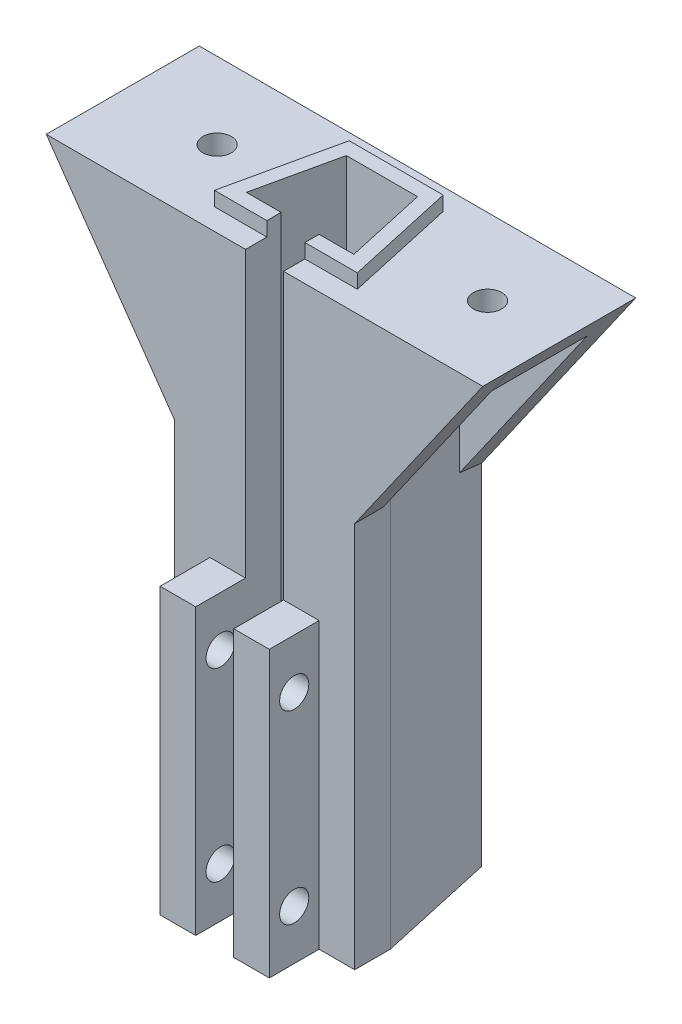
SolidWorks part; units mm, degrees
ref_plane "Front Plane" through (0, 0, 0) normal (0, 0, 1) x (1, 0, 0)
ref_plane "Top Plane" through (0, 0, 0) normal (0, 1, 0) x (1, 0, 0)
ref_plane "Right Plane" through (0, 0, 0) normal (1, 0, 0) x (0, 0, -1)
sketch "Sketch2" plane through (0, 0, 0) normal (0, 1, 0) x (1, 0, 0)
  line L0 (-10.5836, 6.3436) -> (7.4423, 6.3436)
  line L1 (-10.5836, 6.3436) -> (-10.5836, 1.3436)
  line L2 (7.4423, 6.3436) -> (7.4423, 1.3436)
  line L3 (-10.5836, 1.3436) -> (7.4423, 1.3436)
  line L4 (7.4423, 6.3436) -> (11.1002, -10.1564)
  line L5 (7.4423, 6.3436) -> (2.5608, 5.2614)
  line L6 (11.1002, -10.1564) -> (6.2187, -11.2386)
  line L7 (2.5608, 5.2614) -> (6.2187, -11.2386)
  line L8 (-10.5836, 6.3436) -> (-14.2416, -10.1564)
  line L9 (-10.5836, 6.3436) -> (-5.7021, 5.2614)
  line L10 (-14.2416, -10.1564) -> (-9.3601, -11.2386)
  line L11 (-5.7021, 5.2614) -> (-9.3601, -11.2386)
  line L12 (-14.2416, -10.1564) -> (-4.2416, -10.1564)
  line L13 (-14.2416, -10.1564) -> (-14.2416, -15.1564)
  line L14 (-4.2416, -10.1564) -> (-4.2416, -15.1564)
  line L15 (-14.2416, -15.1564) -> (-4.2416, -15.1564)
  line L16 (11.1002, -10.1564) -> (1.1002, -10.1564)
  line L17 (11.1002, -10.1564) -> (11.1002, -15.1564)
  line L18 (1.1002, -10.1564) -> (1.1002, -15.1564)
  line L19 (11.1002, -15.1564) -> (1.1002, -15.1564)
  line L20 (-4.2416, -15.1564) -> (-9.2416, -15.1564)
  line L21 (-4.2416, -15.1564) -> (-4.2416, -22.1564)
  line L22 (-9.2416, -15.1564) -> (-9.2416, -22.1564)
  line L23 (-4.2416, -22.1564) -> (-9.2416, -22.1564)
  line L24 (1.1002, -15.1564) -> (6.1002, -15.1564)
  line L25 (1.1002, -15.1564) -> (1.1002, -22.1564)
  line L26 (6.1002, -15.1564) -> (6.1002, -22.1564)
  line L27 (1.1002, -22.1564) -> (6.1002, -22.1564)
  point P0 (-6.5707, 1.3436)
  point P21 (3.4293, 1.3436)
  point P24 (5.9788, -10.1564)
  point P25 (-9.1202, -10.1564)
  dimension "D1" = 0
  dimension "D2" = 5
  dimension "D3" = 5
  dimension "D4" = 5
  dimension "D5" = 10
  dimension "D6" = 360
  dimension "D7" = 11.5
  dimension "D8" = 5
  dimension "D9" = 5
  dimension "D10" = 11.5
  dimension "D11" = 5
  dimension "D12" = 5
  dimension "D13" = 102.5
  dimension "D14" = 10
  dimension "D15" = 10
  dimension "D16" = 102.5
  dimension "D17" = 15.099
  dimension "D18" = 5.3418
  dimension "D19" = 7
  dimension "D20" = 7
extrude "Boss-Extrude1" add sketch "Sketch2" along normal blind 40 contours L16 L4 L2 L3 L7 | L9 L11 L3 L7 L5 L0 | L8 L12 L11 L3 L1 | L5 L7 L3 L2 | L11 L9 L1 L3 | L13 L15 L14 L12 L11 L10 | L12 L10 L11 | L6 L16 L7 | L19 L17 L6 L7 L16 L18 | L25 L27 L26 L19 | L23 L21 L15 L22 region at (-8.4324, 0, -3.6632) region at (-10.4307, 0, 4.0731) region at (-1.5707, 0, -3.9883) region at (7.2894, 0, 4.0731) region at (5.291, 0, -3.6632) region at (-10.9073, 0, 10.5172) region at (-9.1438, 0, 12.7819) region at (6.0025, 0, 12.7819) region at (7.7659, 0, 10.5172) region at (-6.7416, 0, 18.6564) region at (3.6002, 0, 18.6564)
sketch "Sketch3" plane through (-9.2416, 0, 0) normal (-1, 0, 0) x (0, 0, 1)
  line L0 (22.1564, 40) -> (22.1564, 0) construction
  line L1 (15.1564, 40) -> (15.1564, 0) construction
  line L2 (15.1564, 40) -> (22.1564, 40) construction
  line L3 (15.1564, 0) -> (22.1564, 0) construction
  circle A0 centre (18.6564, 33) radius 2.05
  circle A1 centre (18.6564, 7) radius 2.05
  dimension "D5" = 4.1
  dimension "D6" = 4.1
  dimension "D1" = 3.5
  dimension "D2" = 3.5
  dimension "D3" = 3.5
  dimension "D4" = 3.5
  dimension "D7" = 7
  dimension "D8" = 7
extrude "Cut-Extrude2" cut sketch "Sketch3" against normal blind 40
sketch "Sketch4" plane through (0, 40, 0) normal (0, 1, 0) x (1, 0, 0)
  line L0 (-9.1202, -10.1564) -> (-6.5707, 1.3436)
  line L1 (-6.5707, 1.3436) -> (3.4293, 1.3436)
  line L2 (3.4293, 1.3436) -> (5.9788, -10.1564)
  line L3 (5.9788, -10.1564) -> (1.1002, -10.1564)
  line L4 (1.1002, -10.1564) -> (1.1002, -15.1564)
  line L5 (1.1002, -10.1564) -> (1.1002, -22.1564) construction
  line L6 (1.1002, -15.1564) -> (11.1002, -15.1564)
  line L7 (11.1002, -15.1564) -> (11.1002, -10.1564)
  line L8 (11.1002, -10.1564) -> (7.4423, 6.3436)
  line L9 (7.4423, 6.3436) -> (-10.5836, 6.3436)
  line L10 (-10.5836, 6.3436) -> (-14.2416, -10.1564)
  line L11 (-14.2416, -10.1564) -> (-14.2416, -15.1564)
  line L12 (-14.2416, -15.1564) -> (-4.2416, -15.1564)
  line L13 (-4.2416, -10.1564) -> (-4.2416, -22.1564) construction
  line L14 (-4.2416, -15.1564) -> (-4.2416, -10.1564)
  line L33 (-6.5707, 1.3436) -> (3.4293, 1.3436)
  line L34 (3.4293, 1.3436) -> (5.9788, -10.1564)
  line L35 (5.9788, -10.1564) -> (1.1002, -10.1564)
  line L36 (1.1002, -10.1564) -> (1.1002, -22.1564)
  line L37 (1.1002, -22.1564) -> (6.1002, -22.1564)
  line L38 (6.1002, -22.1564) -> (6.1002, -15.1564)
  line L39 (6.1002, -15.1564) -> (11.1002, -15.1564)
  line L40 (11.1002, -15.1564) -> (11.1002, -10.1564)
  line L41 (11.1002, -10.1564) -> (7.4423, 6.3436)
  line L42 (7.4423, 6.3436) -> (-10.5836, 6.3436)
  line L43 (-10.5836, 6.3436) -> (-14.2416, -10.1564)
  line L44 (-14.2416, -10.1564) -> (-14.2416, -15.1564)
  line L45 (-14.2416, -15.1564) -> (-9.2416, -15.1564)
  line L46 (-9.2416, -15.1564) -> (-9.2416, -22.1564)
  line L47 (-9.2416, -22.1564) -> (-4.2416, -22.1564)
  line L48 (-4.2416, -22.1564) -> (-4.2416, -10.1564)
  line L49 (-4.2416, -10.1564) -> (-9.1202, -10.1564)
  line L50 (-9.1202, -10.1564) -> (-6.5707, 1.3436)
  line L51 (-6.5707, 1.3436) -> (3.4293, 1.3436)
  line L52 (3.4293, 1.3436) -> (5.9788, -10.1564)
  line L53 (5.9788, -10.1564) -> (1.1002, -10.1564)
  line L54 (1.1002, -10.1564) -> (1.1002, -22.1564)
  line L55 (1.1002, -22.1564) -> (6.1002, -22.1564)
  line L56 (6.1002, -22.1564) -> (6.1002, -15.1564)
  line L57 (6.1002, -15.1564) -> (11.1002, -15.1564)
  line L58 (11.1002, -15.1564) -> (11.1002, -10.1564)
  line L59 (11.1002, -10.1564) -> (7.4423, 6.3436)
  line L60 (7.4423, 6.3436) -> (-10.5836, 6.3436)
  line L61 (-10.5836, 6.3436) -> (-14.2416, -10.1564)
  line L62 (-14.2416, -10.1564) -> (-14.2416, -15.1564)
  line L63 (-14.2416, -15.1564) -> (-9.2416, -15.1564)
  line L64 (-9.2416, -15.1564) -> (-9.2416, -22.1564)
  line L65 (-9.2416, -22.1564) -> (-4.2416, -22.1564)
  line L66 (-4.2416, -22.1564) -> (-4.2416, -10.1564)
  line L68 (-9.1202, -10.1564) -> (-6.5707, 1.3436)
  line M19 (-6.5707, 1.3436) -> (3.4293, 1.3436)
  line M20 (3.4293, 1.3436) -> (5.9788, -10.1564)
  line M21 (5.9788, -10.1564) -> (1.1002, -10.1564)
  line M22 (1.1002, -10.1564) -> (1.1002, -22.1564)
  line M25 (6.1002, -15.1564) -> (11.1002, -15.1564)
  line M26 (11.1002, -15.1564) -> (11.1002, -10.1564)
  line M27 (11.1002, -10.1564) -> (7.4423, 6.3436)
  line M28 (7.4423, 6.3436) -> (-10.5836, 6.3436)
  line M29 (-10.5836, 6.3436) -> (-14.2416, -10.1564)
  line M30 (-14.2416, -10.1564) -> (-14.2416, -15.1564)
  line M31 (-14.2416, -15.1564) -> (-9.2416, -15.1564)
  line M34 (-4.2416, -22.1564) -> (-4.2416, -10.1564)
  line M35 (-4.2416, -10.1564) -> (-9.1202, -10.1564)
  line M36 (-9.1202, -10.1564) -> (-6.5707, 1.3436)
  dimension "D1" = 0
extrude "Boss-Extrude2" add sketch "Sketch4" along normal blind 40 contours L12 L6 M31 M34 M35 M36 M19 M20 M21 M22 M25 M26 M27 M28 M29 M30 region at (-6.6809, 40, 10.4888)
sketch "Sketch7" plane through (0, 0, -6.3436) normal (0, 0, -1) x (-1, 0, 0)
  line L0 (-7.4423, 82) -> (-7.4423, 0) construction
  line L1 (3.3202, 3.2) -> (-0.1798, 3.2)
  line L2 (3.3202, 3.2) -> (3.3202, 4.4)
  line L3 (3.3202, 4.4) -> (-0.1798, 4.4)
  line L4 (-0.1798, 3.2) -> (-0.1798, 4.4)
  line L5 (10.5836, 82) -> (10.5836, 0) construction
  line L6 (10.5836, 0) -> (-7.4423, 0) construction
  point P4 (-0.1798, 3.8)
  dimension "D1" = 7.2625
  dimension "D2" = 3.5
  dimension "D3" = 1.2
  dimension "D4" = 7.2633
  dimension "D5" = 3.2
extrude "Cut-Extrude3" cut sketch "Sketch7" against normal through all
sketch "Sketch8" plane through (0, 0, 10.1564) normal (0, 0, -1) x (-1, 0, 0)
  line L0 (4.2416, 80) -> (4.2416, 0) construction
  line L1 (5.2416, 4.4) -> (4.2416, 4.4)
  line L2 (5.2416, 4.4) -> (5.2416, 3.2)
  line L3 (5.2416, 3.2) -> (4.2416, 3.2)
  line L4 (4.2416, 4.4) -> (4.2416, 3.2)
  line L5 (9.1202, 0) -> (4.2416, 0) construction
  dimension "D1" = 1.2
  dimension "D2" = 1
  dimension "D3" = 3.2
extrude "Cut-Extrude4" cut sketch "Sketch8" against normal blind 5
sketch "Sketch9" plane through (0, 80, 0) normal (0, 1, 0) x (1, 0, 0)
  line L0 (1.1002, -10.1564) -> (1.1002, -12.1564)
  line L1 (1.1002, -10.1564) -> (1.1002, -15.1564) construction
  line L2 (1.1002, -10.1564) -> (5.9788, -10.1564)
  line L3 (5.9788, -10.1564) -> (3.4293, 1.3436)
  line L4 (3.4293, 1.3436) -> (-6.5707, 1.3436)
  line L5 (-6.5707, 1.3436) -> (-9.1202, -10.1564)
  line L6 (-9.1202, -10.1564) -> (-4.2416, -10.1564)
  line L7 (-4.2416, -10.1564) -> (-4.2416, -12.1564)
  line L8 (-4.2416, -15.1564) -> (-4.2416, -10.1564) construction
  line L9 (-4.2416, -12.1564) -> (-11.6121, -12.1564)
  line L10 (-11.6121, -12.1564) -> (-8.1758, 3.3436)
  line L11 (-8.1758, 3.3436) -> (5.0345, 3.3436)
  line L12 (5.0345, 3.3436) -> (8.4708, -12.1564)
  line L13 (8.4708, -12.1564) -> (1.1002, -12.1564)
  dimension "D1" = 2
  dimension "D2" = 2
  dimension "D3" = 2
  dimension "D4" = 2
  dimension "D5" = 2
  dimension "D6" = 13.2103
extrude "Boss-Extrude3" add sketch "Sketch9" along normal blind 2
sketch "Sketch10" plane through (-5.2416, 0, 0) normal (1, 0, 0) x (0, 0, -1)
  line L0 (-15.1564, 4.4) -> (-10.1564, 4.4) construction
  line L1 (-15.1564, 3.2) -> (-13.1564, 3.2)
  line L2 (-15.1564, 3.2) -> (-15.1564, 4.4)
  line L3 (-15.1564, 4.4) -> (-13.1564, 4.4)
  line L4 (-13.1564, 3.2) -> (-13.1564, 4.4)
  dimension "D1" = 2
extrude "Cut-Extrude5" cut sketch "Sketch10" against normal blind 11
sketch "Sketch11" plane through (0, 0, 15.1564) normal (0, 0, 1) x (1, 0, 0)
  line L0 (11.1002, 54.2933) -> (29.1002, 80)
  line L1 (11.1002, 80) -> (11.1002, 0) construction
  line L2 (29.1002, 80) -> (11.1002, 80)
  line L3 (11.1002, 80) -> (11.1002, 54.2933)
  line L4 (-14.2416, 54.2933) -> (-32.2416, 80)
  line L5 (-14.2416, 80) -> (-14.2416, 4.4) construction
  line L6 (-32.2416, 80) -> (-14.2416, 80)
  line L7 (-14.2416, 80) -> (-14.2416, 54.2933)
  dimension "D1" = 18
  dimension "D2" = 18
  dimension "D3" = 55
  dimension "D4" = 55
extrude "Boss-Extrude4" add sketch "Sketch11" against normal blind 4
sketch "Sketch15" plane through (0, 0, -6.3436) normal (0, 0, -1) x (-1, 0, 0)
  line L0 (-7.4423, 80) -> (-7.4423, 49.0806)
  line L1 (-7.4423, 80) -> (-7.4423, 0) construction
  line L2 (-7.4423, 49.0806) -> (-29.0923, 80)
  line L3 (-29.0923, 80) -> (-7.4423, 80)
  line L4 (10.5836, 80) -> (10.5836, 49.0806)
  line L5 (10.5836, 80) -> (10.5836, 0) construction
  line L6 (10.5836, 49.0806) -> (32.2336, 80)
  line L7 (32.2336, 80) -> (10.5836, 80)
  dimension "D1" = 55
  dimension "D2" = 21.65
  dimension "D3" = 55
  dimension "D4" = 21.65
extrude "Boss-Extrude7" add sketch "Sketch15" against normal blind 4
sketch "Sketch16" plane through (0, 0, -6.3436) normal (0, 0, -1) x (-1, 0, 0)
  line L0 (32.2336, 80) -> (29.4328, 76)
  line L1 (10.5836, 49.0806) -> (32.2336, 80) construction
  line L2 (29.4328, 76) -> (10.2336, 76)
  line L3 (10.2336, 76) -> (10.2336, 80)
  line L4 (-29.0923, 80) -> (32.2336, 80) construction
  line L5 (10.2336, 80) -> (32.2336, 80)
  line L6 (-29.0923, 80) -> (-26.2914, 76)
  line L7 (-29.0923, 80) -> (-7.4423, 49.0806) construction
  line L8 (-26.2914, 76) -> (-7.0923, 76)
  line L9 (-7.0923, 76) -> (-7.0923, 80)
  line L10 (-7.0923, 80) -> (-29.0923, 80)
  dimension "D1" = 22
  dimension "D2" = 22
  dimension "D3" = 4
  dimension "D4" = 4
extrude "Boss-Extrude8" add sketch "Sketch16" against normal blind 19
sketch "Sketch17" plane through (0, 76, 0) normal (0, -1, 0) x (-1, 0, 0)
  line L0 (11.4704, 2.3436) -> (29.4328, 2.3436) construction
  line L1 (29.4328, -11.1564) -> (14.2416, -11.1564) construction
  line L2 (-26.2914, -11.1564) -> (-11.1002, -11.1564) construction
  line L3 (-26.2914, -11.1564) -> (-26.2914, 2.3436) construction
  line L4 (29.4328, -11.1564) -> (29.4328, 2.3436) construction
  circle A0 centre (-19.0195, -4.4064) radius 2
  circle A1 centre (18.9805, -4.4064) radius 2
  dimension "D1" = 4
  dimension "D2" = 4
  dimension "D3" = 6.75
  dimension "D4" = 6.75
  dimension "D5" = 6.75
  dimension "D6" = 7.272
  dimension "D7" = 10.4522
extrude "Cut-Extrude7" cut sketch "Sketch17" against normal blind 19
